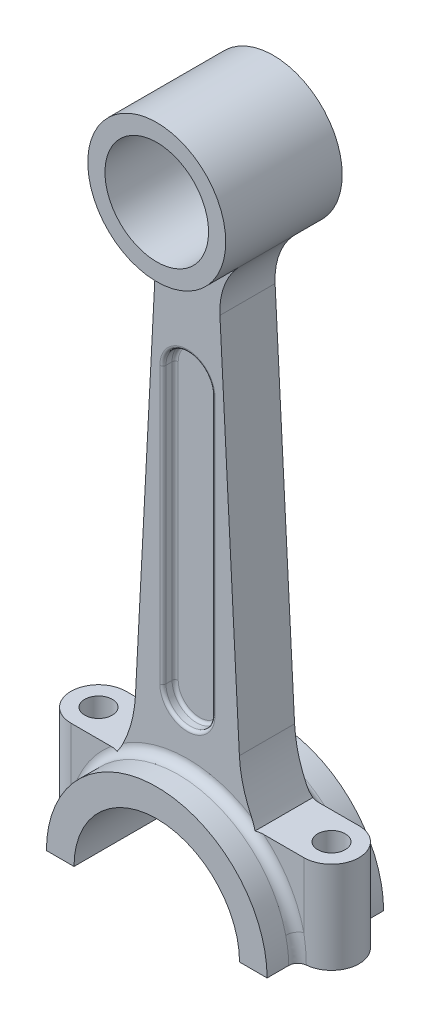
SolidWorks part; units mm, degrees
ref_plane "Front Plane" through (0, 0, 0) normal (0, 0, 1) x (1, 0, 0)
ref_plane "Top Plane" through (0, 0, 0) normal (0, 1, 0) x (1, 0, 0)
ref_plane "Right Plane" through (0, 0, 0) normal (1, 0, 0) x (0, 0, -1)
sketch "Sketch1" plane through (0, 0, 0) normal (0, 0, 1) x (1, 0, 0)
  line L0 (0, 0) -> (0, -201.2) construction
  line L1 (-10, -20.1556) -> (-17.8497, -169.9368)
  line L2 (10, -20.1556) -> (17.8497, -169.9368)
  line L3 (-36, -201.2) -> (-27, -201.2)
  line L4 (27, -201.2) -> (36, -201.2)
  circle A0 centre (0, 0) radius 22.5
  circle A1 centre (0, 0) radius 16.9
  arc A2 (27, -201.2) -> (-27, -201.2) centre (0, -201.2) ccw
  arc A3 (36, -201.2) -> (-36, -201.2) centre (0, -201.2) ccw
  dimension "D1" = 45
  dimension "D2" = 33.8
  dimension "D3" = 54
  dimension "D4" = 72
  dimension "D5" = 201.2
  dimension "D6" = 20
  dimension "D7" = 6
extrude "Boss-Extrude1" add sketch "Sketch1" along normal mid plane 38 contours A1 A0 | A3 A2 | L0 A3 L3 A2 region at (-4.9903, -21.2865, 0) region at (20.1899, -181.0101, 0) region at (-20.1899, -181.0101, 0)
extrude "Boss-Extrude2" add sketch "Sketch1<3>" along normal mid plane 18 contours A0 L0 A3 L2 | L0 A0 L1 A3 region at (7.1843, -100.8455, 0) region at (-7.1843, -100.8455, 0)
sketch "Sketch1<3>" plane through (0, 0, 0) normal (0, 0, 1) x (1, 0, 0) same geometry as "Sketch1"
sketch "Sketch2" plane through (0, 0, 9) normal (0, 0, 1) x (1, 0, 0)
  line L0 (0, 0) -> (0, -201.2) construction
  line L1 (0, -145.6) -> (0, -55.6) construction
  line L2 (-8, -145.6) -> (-8, -55.6)
  line L3 (8, -145.6) -> (8, -55.6)
  arc A0 (-8, -145.6) -> (8, -145.6) centre (0, -145.6) ccw
  arc A1 (8, -55.6) -> (-8, -55.6) centre (0, -55.6) ccw
  point P6 (0, -100.6)
  dimension "D2" = 8
  dimension "D1" = 90
extrude "Cut-Extrude1" cut sketch "Sketch2" against normal blind 4
mirror "Mirror1" about plane through (0, 0, 0) normal (0, 0, 1) of "Cut-Extrude1"
fillet "Fillet1" radius 1 8 edges at (0, -47.6, 9) (8, -100.6, 9) (-8, -100.6, 5) (0, -47.6, 5) (8, -100.6, 5) (0, -153.6, 5) (0, -153.6, 9) (-8, -100.6, 9)
fillet "Fillet3" radius 40 2 edges at (17.8497, -169.9368, 0) (-17.8497, -169.9368, 0)
fillet "Fillet4" radius 22.5 2 edges at (-10, -20.1556, 0) (10, -20.1556, 0)
ref_plane "Plane2" through (0, -171.2, 0) normal (0, -1, 0) x (-1, 0, 0)
sketch "Sketch4" plane through (0, -171.2, 0) normal (0, -1, 0) x (-1, 0, 0)
  line L0 (38, 0) -> (-38, 0) construction
  line L1 (38, -9) -> (-38, -9)
  line L2 (38, 9) -> (-38, 9)
  arc A0 (38, -9) -> (38, 9) centre (38, 0) ccw
  arc A1 (-38, 9) -> (-38, -9) centre (-38, 0) ccw
  point P2 (0, 0)
  dimension "D2" = 9
  dimension "D1" = 76
extrude "Boss-Extrude3" add sketch "Sketch4" along normal up to surface (30 mm away) up to face at (-31.5, -201.2, 0)
sketch "Sketch5" plane through (0, 0, 9) normal (0, 0, 1) x (1, 0, 0)
  line L1 (-27, -201.2) -> (27, -201.2)
  line L2 (-27, -201.2) -> (27, -201.2)
  arc A1 (27, -201.2) -> (-27, -201.2) centre (0, -201.2) ccw
  arc A2 (27, -201.2) -> (-27, -201.2) centre (0, -201.2) ccw
  dimension "D1" = 0
extrude "Cut-Extrude2" cut sketch "Sketch5" against normal through all
sketch "Sketch6" plane through (0, -171.2, 0) normal (0, 1, 0) x (1, 0, 0)
  circle A0 centre (-38, 0) radius 4.5
  circle A1 centre (38, 0) radius 4.5
  dimension "D1" = 9
  dimension "D2" = 9
extrude "Cut-Extrude3" cut sketch "Sketch6" against normal through all
fillet "Fillet5" radius 3 2 edges at (0, -165.2, -9) (0, -165.2, 9)
